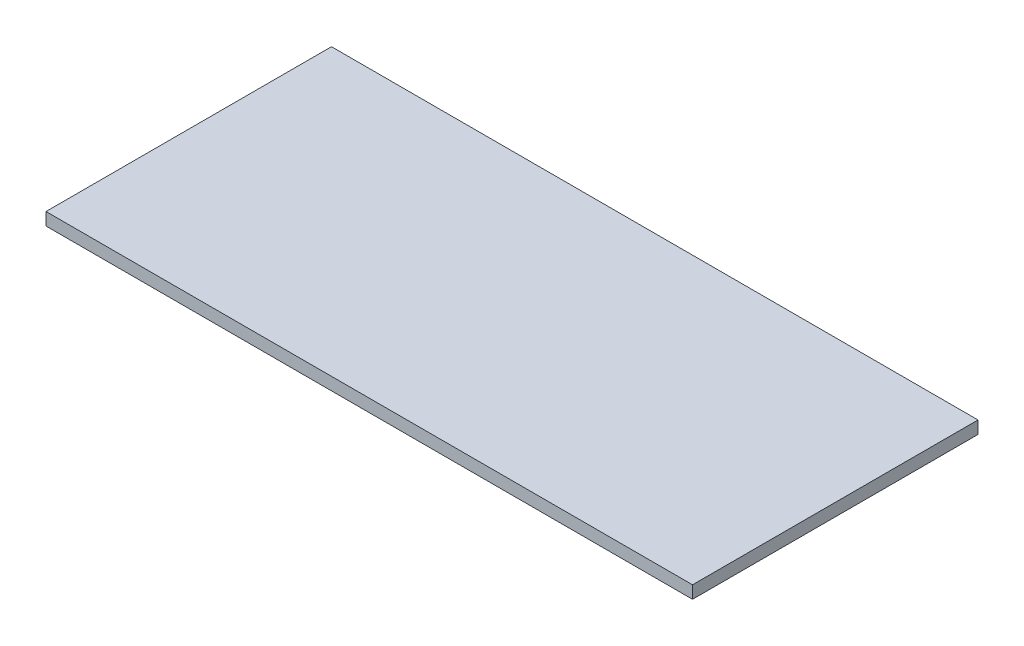
SolidWorks part; units mm, degrees
ref_plane "Front Plane" through (0, 0, 0) normal (0, 0, 1) x (1, 0, 0)
ref_plane "Top Plane" through (0, 0, 0) normal (0, 1, 0) x (1, 0, 0)
ref_plane "Right Plane" through (0, 0, 0) normal (1, 0, 0) x (0, 0, -1)
sketch "Sketch1" plane through (0, 0, 0) normal (0, 1, 0) x (1, 0, 0)
  line L1 (488.95, -215.9) -> (-488.95, -215.9)
  line L2 (488.95, -215.9) -> (488.95, 215.9)
  line L3 (488.95, 215.9) -> (-488.95, 215.9)
  line L4 (-488.95, -215.9) -> (-488.95, 215.9)
  line L5 (488.95, -215.9) -> (-488.95, 215.9) construction
  line L6 (488.95, 215.9) -> (-488.95, -215.9) construction
  point P0 (0, 0)
  dimension "D1" = 431.8
  dimension "D2" = 977.9
extrude "Glass" add sketch "Sketch1" along normal blind 19.05
